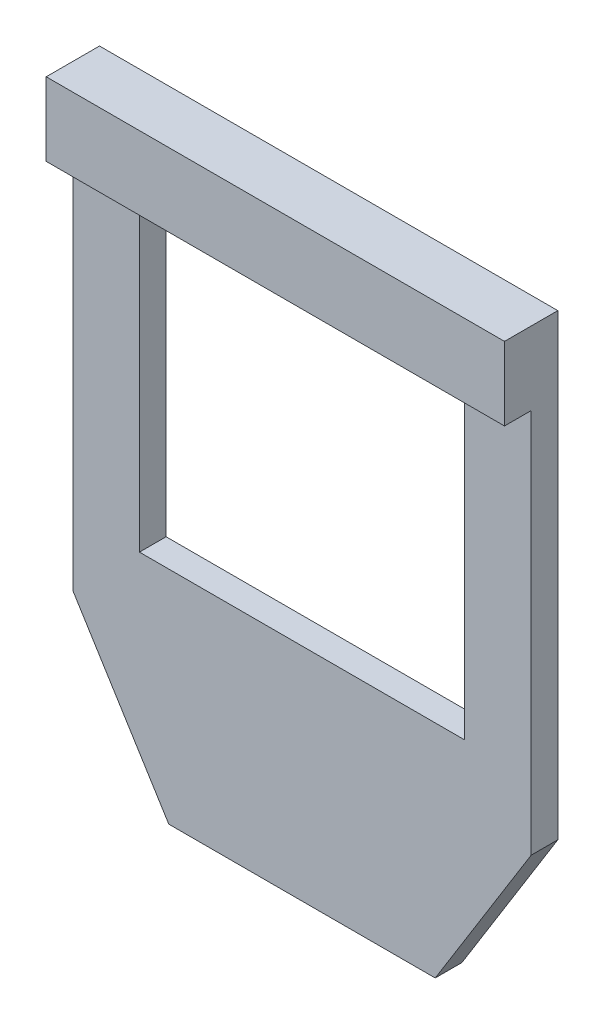
SolidWorks part; units mm, degrees
ref_plane "Front" through (0, 0, 0) normal (0, 0, 1) x (1, 0, 0)
ref_plane "Top" through (0, 0, 0) normal (0, 1, 0) x (1, 0, 0)
ref_plane "Right" through (0, 0, 0) normal (1, 0, 0) x (0, 0, -1)
sketch "Sketch1" plane through (0, 0, 0) normal (0, 0, 1) x (1, 0, 0)
  line L0 (-64.1816, 136.6499) -> (-64.1816, -35.3501)
  line L1 (-64.1816, 136.6499) -> (107.8184, 136.6499)
  line L2 (21.8184, -10.3501) -> (21.8184, -173.6926) construction
  line L4 (107.8184, 136.6499) -> (107.8184, -35.3501)
  line L5 (-39.1816, 111.6499) -> (82.8184, 111.6499)
  line L6 (-64.1816, -35.3501) -> (-28.1802, -93.2631)
  line L7 (-39.1816, -10.3501) -> (82.8184, -10.3501)
  line L8 (82.8184, 111.6499) -> (82.8184, -10.3501)
  line L9 (71.817, -93.2631) -> (107.8184, -35.3501)
  line L10 (-39.1816, 111.6499) -> (-39.1816, -10.3501)
  line L11 (-39.1816, 136.6499) -> (107.8184, 136.6499) construction
  line L12 (-39.1816, -35.3501) -> (107.8184, -35.3501) construction
  line L13 (-64.1816, -60.3501) -> (132.8184, -60.3501) construction
  line L14 (-64.1816, 161.6499) -> (-64.1816, -60.3501) construction
  line L15 (-39.1816, 136.6499) -> (-39.1816, -35.3501) construction
  line L16 (-64.1816, 161.6499) -> (132.8184, 161.6499) construction
  line L17 (132.8184, 161.6499) -> (132.8184, -60.3501) construction
  line L18 (-28.1802, -93.2631) -> (71.817, -93.2631)
  dimension "D1" = 122
  dimension "D2" = 25
  dimension "D3" = 25
  dimension "D5" = 122
  dimension "D7" = 90
  dimension "D6" = 25
extrude "Boss-Extrude1" add sketch "Sketch1" along normal blind 10
sketch "Sketch2" plane through (0, 0, 10) normal (0, 0, 1) x (1, 0, 0)
  line L0 (107.8184, -35.3501) -> (107.8184, 136.6499) construction
  line L1 (-64.1816, 136.6499) -> (107.8184, 136.6499)
  line L2 (-64.1816, 136.6499) -> (-64.1816, 109.1499)
  line L3 (-64.1816, 109.1499) -> (107.8184, 109.1499)
  line L4 (107.8184, 136.6499) -> (107.8184, 109.1499)
  line L5 (82.8184, 111.6499) -> (-39.1816, 111.6499) construction
  dimension "D1" = 2.5
extrude "Boss-Extrude2" add sketch "Sketch2" along normal blind 10
